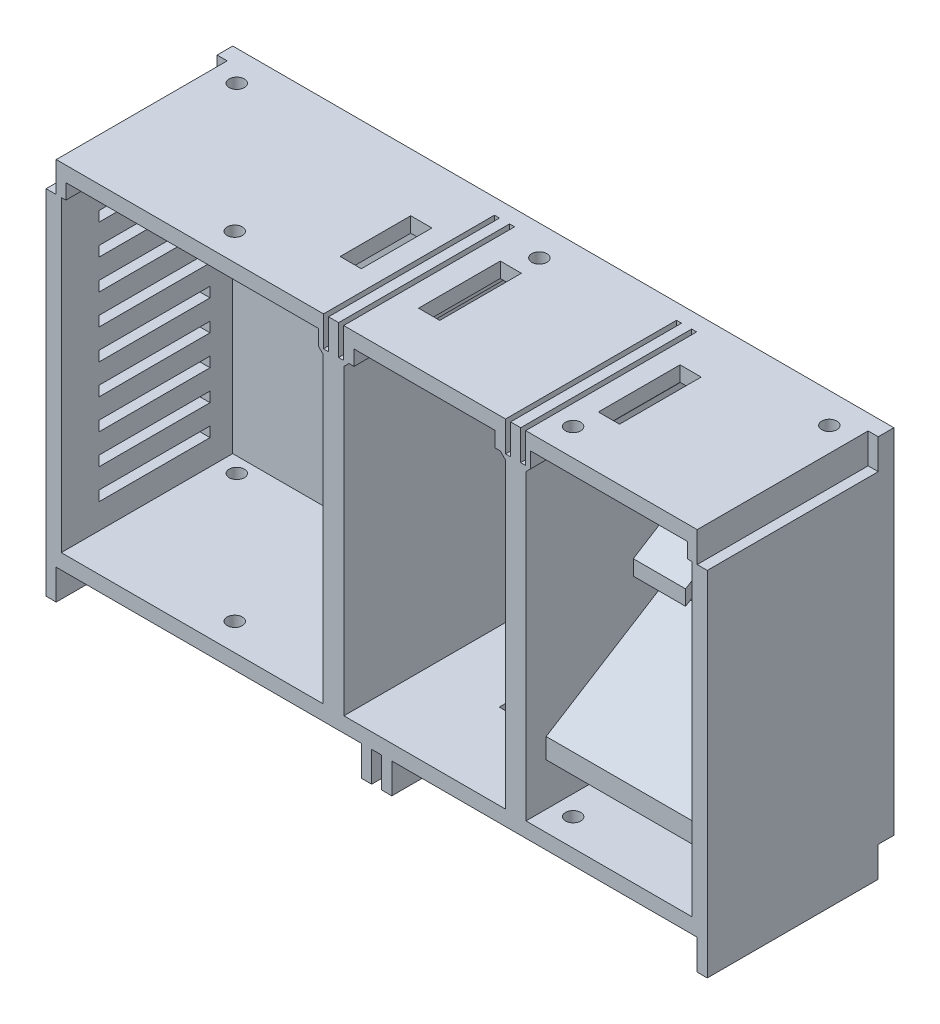
SolidWorks part; units mm, degrees
material "ABS"
ref_plane "Alzado" through (0, 0, 0) normal (0, 0, 1) x (1, 0, 0)
ref_plane "Planta" through (0, 0, 0) normal (0, 1, 0) x (1, 0, 0)
ref_plane "Vista lateral" through (0, 0, 0) normal (1, 0, 0) x (0, 0, -1)
sketch "Croquis1" plane through (0, 0, 0) normal (0, 0, 1) x (1, 0, 0)
  line L0 (0, 0) -> (2, 0)
  line L1 (2, 0) -> (2, 6)
  line L2 (55, 0) -> (55, 6)
  line L3 (55, 6) -> (2, 6)
  line L4 (56, 0) -> (56, 6)
  line L5 (56, 6) -> (58, 6)
  line L6 (58, 6) -> (58, 0)
  line L7 (58, 0) -> (59, 0)
  line L8 (59, 0) -> (59, 6)
  line L9 (91.1, 0) -> (91.1, 6)
  line L10 (59, 6) -> (91.1, 6)
  line L11 (92.1, 0) -> (92.1, 6)
  line L12 (92.1, 6) -> (94.1, 6)
  line L13 (94.1, 6) -> (94.1, 0)
  line L14 (95.1, 0) -> (95.1, 6)
  line L15 (129.1, 0) -> (129.1, 6)
  line L16 (129.1, 6) -> (95.1, 6)
  line L17 (0, 0) -> (0, -64)
  line L18 (0, -64) -> (131.1, -64)
  line L19 (131.1, -64) -> (131.1, 0)
  line L20 (55, 0) -> (56, 0)
  line L21 (58, 0) -> (59, 0)
  line L22 (129.1, 0) -> (131.1, 0)
  line L23 (94.1, 0) -> (95.1, 0)
  line L24 (91.1, 0) -> (92.1, 0)
  line L25 (2, 0) -> (129.1, 0)
  point P3 (2, 0)
  point P4 (129.1, 0)
  point P5 (55, 0)
  point P10 (56, 0)
  point P11 (58, 0)
  point P12 (59, 0)
  point P15 (91.1, 0)
  point P22 (92.1, 0)
  point P23 (94.1, 0)
  point P24 (95.1, 0)
  dimension "D1" = 131.1
  dimension "D2" = 2
  dimension "D3" = 2
  dimension "D4" = 55
  dimension "D5" = 6
  dimension "D6" = 1
  dimension "D7" = 2
  dimension "D8" = 1
  dimension "D9" = 32.1
  dimension "D10" = 1
  dimension "D11" = 2
  dimension "D12" = 1
  dimension "D13" = 64
extrude "Saliente-Extruir1" add sketch "Croquis1" along normal blind 34 contours L8 L25 L9 L10 | L1 L25 L2 L3 | L14 L25 L15 L16 | L11 L25 L13 L12 | L4 L25 L6 L5 region at (28.5, 3, 0) region at (57, 3, 0) region at (112.1, 3, 0) region at (75.05, 3, 0) region at (93.1, 3, 0)
sketch "Croquis2" plane through (0, 0, 0) normal (0, 0, 1) x (1, 0, 0)
  line L1 (2, -64) -> (129.1, -64)
  line L3 (129.1, 0) -> (2, 0)
  line L5 (129.1, 0) -> (131.1, 0)
  line L7 (129.1, -64) -> (131.1, -64)
  line L8 (131.1, 0) -> (131.1, -64)
  line L9 (2, -64) -> (0, -64)
  line L11 (2, 0) -> (0, 0)
  line L12 (0, -64) -> (0, 0)
  dimension "D1" = 64
  dimension "D2" = 2
  dimension "D3" = 2
extrude "Saliente-Extruir2" add sketch "Croquis2" along normal blind 3
sketch "Croquis3" plane through (0, 0, 3) normal (0, 0, 1) x (1, 0, 0)
  line L0 (0, -64) -> (131.1, -64) construction
  line L1 (131.1, 0) -> (128.1, 0)
  line L2 (131.1, 0) -> (131.1, -64)
  line L3 (131.1, -64) -> (128.1, -64)
  line L4 (128.1, 0) -> (128.1, -61)
  line L6 (0, 0) -> (3, 0)
  line L7 (0, 0) -> (0, -64)
  line L8 (0, -64) -> (3, -64)
  line L9 (3, 0) -> (3, -61)
  line L10 (3, -64) -> (128.1, -64)
  line L12 (3, -61) -> (128.1, -61)
  dimension "D1" = 3
  dimension "D2" = 3
  dimension "D3" = 3
extrude "Saliente-Extruir3" add sketch "Croquis3" along normal up to vertex (31 mm away) up to point (129.1, 0, 34)
sketch "Croquis4" plane through (0, 0, 0) normal (0, 0, -1) x (-1, 0, 0)
  line L24 (-59, 0) -> (-59, 6)
  line L25 (-59, 6) -> (-91.1, 6)
  line L26 (-91.1, 6) -> (-91.1, 0)
  line L27 (-91.1, 0) -> (-92.1, 0)
  line L28 (-92.1, 0) -> (-92.1, 6)
  line L29 (-92.1, 6) -> (-94.1, 6)
  line L30 (-94.1, 6) -> (-94.1, 0)
  line L31 (-94.1, 0) -> (-95.1, 0)
  line L32 (-95.1, 0) -> (-95.1, 6)
  line L33 (-95.1, 6) -> (-129.1, 6)
  line L34 (-129.1, 6) -> (-129.1, 0)
  line L35 (-129.1, 0) -> (-131.1, 0)
  line L36 (-131.1, 0) -> (-131.1, -64)
  line L37 (-131.1, -64) -> (0, -64)
  line L38 (0, -64) -> (0, 0)
  line L39 (0, 0) -> (-2, 0)
  line L40 (-2, 0) -> (-2, 6)
  line L41 (-2, 6) -> (-55, 6)
  line L42 (-55, 6) -> (-55, 0)
  line L43 (-55, 0) -> (-56, 0)
  line L44 (-56, 0) -> (-56, 6)
  line L45 (-56, 6) -> (-58, 6)
  line L46 (-58, 6) -> (-58, 0)
  line L47 (-58, 0) -> (-59, 0)
  line L48 (-59, 0) -> (-59, 6)
  line L49 (-59, 6) -> (-91.1, 6)
  line L50 (-91.1, 6) -> (-91.1, 0)
  line L51 (-91.1, 0) -> (-92.1, 0)
  line L52 (-92.1, 0) -> (-92.1, 6)
  line L53 (-92.1, 6) -> (-94.1, 6)
  line L54 (-94.1, 6) -> (-94.1, 0)
  line L55 (-94.1, 0) -> (-95.1, 0)
  line L56 (-95.1, 0) -> (-95.1, 6)
  line L57 (-95.1, 6) -> (-129.1, 6)
  line L58 (-129.1, 6) -> (-129.1, 0)
  line L59 (-129.1, 0) -> (-131.1, 0)
  line L60 (-131.1, 0) -> (-131.1, -64)
  line L61 (-131.1, -64) -> (0, -64)
  line L62 (0, -64) -> (0, 0)
  line L63 (0, 0) -> (-2, 0)
  line L64 (-2, 0) -> (-2, 6)
  line L65 (-2, 6) -> (-55, 6)
  line L66 (-55, 6) -> (-55, 0)
  line L67 (-55, 0) -> (-56, 0)
  line L68 (-56, 0) -> (-56, 6)
  line L69 (-56, 6) -> (-58, 6)
  line L70 (-58, 6) -> (-58, 0)
  line L71 (-58, 0) -> (-59, 0)
  dimension "D1" = 0
extrude "Saliente-Extruir4" add sketch "Croquis4" along normal blind 3
sketch "Croquis5" plane through (0, 0, 3) normal (0, 0, 1) x (1, 0, 0)
  line L1 (128.1, -61) -> (3, -61) construction
  line L23 (54.95, 0.05) -> (59.05, 0.05)
  line L24 (55, 0) -> (55, 6) construction
  line L25 (59, 0) -> (59, 6) construction
  line L26 (58, 0) -> (56, 0) construction
  line L27 (54.95, 0.05) -> (54.95, -61)
  line L28 (59.05, 0.05) -> (59.05, -61)
  line L29 (91.05, 0.05) -> (95.15, 0.05)
  line L30 (91.1, 0) -> (91.1, 6) construction
  line L31 (95.1, 0) -> (95.1, 6) construction
  line L32 (95.1, 0) -> (94.1, 0) construction
  line L33 (91.05, 0.05) -> (91.05, -61)
  line L34 (128.1, -61) -> (3, -61) construction
  line L35 (91.05, -61) -> (95.15, -61)
  line L36 (95.15, -61) -> (95.15, 0.05)
  line M6 (128.1, 0) -> (95.1, 0)
  line M7 (95.1, 0) -> (94.1, 0)
  line M8 (94.1, 0) -> (92.1, 0)
  line M9 (92.1, 0) -> (91.1, 0)
  line M10 (91.1, 0) -> (59, 0)
  line M11 (59, 0) -> (58, 0)
  line M12 (58, 0) -> (56, 0)
  line M13 (56, 0) -> (55, 0)
  line M14 (55, 0) -> (3, 0)
  line M16 (3, -61) -> (128.1, -61)
  dimension "D1" = 0.05
  dimension "D2" = 0.05
  dimension "D3" = 0.05
  dimension "D4" = 0.05
  dimension "D5" = 0.05
  dimension "D6" = 0.05
extrude "Saliente-Extruir10" add sketch "Croquis5" along normal up to vertex (31 mm away) contours L28 L27 M10 M11 M12 M13 M14 M16 | L36 L33 M16 M6 M7 M8 M9 M10 region at (57, -30.5, 3) region at (93.1, -30.5, 3) up to point (59, 0, 34)
sketch "Croquis6" plane through (0, 0, 0) normal (0, -1, 0) x (1, 0, 0)
  line L0 (0, 34) -> (0, -3) construction
  line L1 (0, 15.5) -> (131.1, 15.5) construction
  line L2 (131.1, 34) -> (131.1, -3) construction
  line L3 (51, 8.5) -> (51, 22.5)
  line L4 (51, 22.5) -> (46.8, 22.5)
  line L5 (46.8, 22.5) -> (46.8, 8.5)
  line L6 (46.8, 8.5) -> (51, 8.5)
  line L7 (99.1, 7.4) -> (99.1, 23.6)
  line L8 (99.1, 23.6) -> (103.3, 23.6)
  line L9 (103.3, 23.6) -> (103.3, 7.4)
  line L10 (103.3, 7.4) -> (99.1, 7.4)
  line L11 (63.45, 7.4) -> (63.45, 23.6)
  line L12 (63.45, 23.6) -> (67.65, 23.6)
  line L13 (67.65, 23.6) -> (67.65, 7.4)
  line L14 (67.65, 7.4) -> (63.45, 7.4)
  point P6 (99.1, 15.5)
  point P9 (51, 15.5)
  point P15 (99.1, 15.5)
  point P17 (63.45, 15.5)
  point P21 (63.45, 15.5)
  dimension "D1" = 51
  dimension "D2" = 4.2
  dimension "D3" = 14
  dimension "D4" = 32
  dimension "D5" = 16.2
  dimension "D6" = 4.2
  dimension "D7" = 12.45
extrude "Cortar-Extruir1" cut sketch "Croquis6" against normal up to next
sketch "Croquis7" plane through (0, 0, 34) normal (0, 0, 1) x (1, 0, 0)
  line L0 (3, 0) -> (54.95, 0) construction
  line L1 (28.975, 0) -> (28.975, 3)
  line L2 (3.925, 3) -> (54.025, 3)
  line L3 (54.025, 3) -> (54.025, 0)
  line L4 (3.925, 0) -> (54.025, 0)
  line L5 (3.925, 3) -> (3.925, 0)
  line L6 (75.05, 0) -> (75.05, 3)
  line L7 (59.05, 0) -> (91.05, 0) construction
  line L8 (75.05, 3) -> (89.05, 3)
  line L9 (89.05, 3) -> (89.05, 0)
  line L10 (89.05, 0) -> (75.05, 0)
  line L11 (75.05, 3) -> (61.05, 3)
  line L12 (61.05, 3) -> (61.05, 0)
  line L13 (61.05, 0) -> (75.05, 0)
  line L14 (61.05, 3) -> (75.05, 3)
  line L15 (111.625, 0) -> (111.625, 3)
  line L16 (95.15, 0) -> (128.1, 0) construction
  line L17 (111.625, 3) -> (127.225, 3)
  line L18 (127.225, 3) -> (127.225, 0)
  line L19 (127.225, 0) -> (111.625, 0)
  line L20 (111.625, 0) -> (96.025, 0)
  line L21 (96.025, 0) -> (96.025, 3)
  line L22 (96.025, 3) -> (111.625, 3)
  line M5 (59.05, 0) -> (91.05, 0)
  line M10 (95.15, 0) -> (128.1, 0)
  line M37 (3, 0) -> (54.95, 0)
  dimension "D1" = 25.05
  dimension "D2" = 3
  dimension "D3" = 14
  dimension "D4" = 15.6
extrude "Cortar-Extruir2" cut sketch "Croquis7" against normal up to vertex (31 mm away) contours L3 L2 L1 M37 | L2 L5 L1 M37 | L11 L12 L6 M5 | L9 L8 L6 M5 | L22 L21 L15 M10 | L18 L17 L15 M10 region at (16.45, 1.5, 34) region at (41.5, 1.5, 34) region at (68.05, 1.5, 34) region at (82.05, 1.5, 34) region at (103.825, 1.5, 34) region at (119.425, 1.5, 34) up to point (54.95, 0, 3)
sketch "Croquis22" plane through (0, 0, 3) normal (0, 0, 1) x (1, 0, 0)
  line L0 (95.15, 0) -> (95.15, -61) construction
  line L1 (95.15, -61) -> (128.1, -61) construction
  line L2 (128.1, -61) -> (128.1, 0) construction
  line L3 (128.1, 0) -> (127.225, 0) construction
  line L4 (127.225, 0) -> (127.225, 3) construction
  line L5 (127.225, 3) -> (96.025, 3) construction
  line L6 (96.025, 3) -> (96.025, 0) construction
  line L7 (96.025, 0) -> (95.15, 0) construction
  line L8 (91.05, -61) -> (91.05, 0) construction
  line L9 (91.05, 0) -> (89.05, 0) construction
  line L10 (89.05, 0) -> (89.05, 3) construction
  line L11 (89.05, 3) -> (61.05, 3) construction
  line L12 (61.05, 3) -> (61.05, 0) construction
  line L13 (61.05, 0) -> (59.05, 0) construction
  line L14 (59.05, 0) -> (59.05, -61) construction
  line L15 (59.05, -61) -> (91.05, -61) construction
  line L16 (54.95, -61) -> (54.95, 0) construction
  line L17 (54.95, 0) -> (54.025, 0) construction
  line L18 (54.025, 0) -> (54.025, 3) construction
  line L19 (54.025, 3) -> (3.925, 3) construction
  line L20 (3.925, 3) -> (3.925, 0) construction
  line L21 (3.925, 0) -> (3, 0) construction
  line L22 (3, 0) -> (3, -61) construction
  line L23 (3, -61) -> (54.95, -61) construction
  line L24 (95.15, 0) -> (95.15, -61)
  line L25 (95.15, -61) -> (128.1, -61)
  line L26 (128.1, -61) -> (128.1, 0)
  line L27 (128.1, 0) -> (127.225, 0)
  line L28 (127.225, 0) -> (127.225, 3)
  line L29 (127.225, 3) -> (96.025, 3)
  line L30 (96.025, 3) -> (96.025, 0)
  line L31 (96.025, 0) -> (95.15, 0)
  line L32 (91.05, -61) -> (91.05, 0)
  line L33 (91.05, 0) -> (89.05, 0)
  line L34 (89.05, 0) -> (89.05, 3)
  line L35 (89.05, 3) -> (61.05, 3)
  line L36 (61.05, 3) -> (61.05, 0)
  line L37 (61.05, 0) -> (59.05, 0)
  line L38 (59.05, 0) -> (59.05, -61)
  line L39 (59.05, -61) -> (91.05, -61)
  line L40 (54.95, -61) -> (54.95, 0)
  line L41 (54.95, 0) -> (54.025, 0)
  line L42 (54.025, 0) -> (54.025, 3)
  line L43 (54.025, 3) -> (3.925, 3)
  line L44 (3.925, 3) -> (3.925, 0)
  line L45 (3.925, 0) -> (3, 0)
  line L46 (3, 0) -> (3, -61)
  line L47 (3, -61) -> (54.95, -61)
extrude "Cortar-Extruir8" cut sketch "Croquis22" against normal blind 3 contours L40 L41 L42 L43 L44 L45 L46 L47 | L32 L33 L34 L35 L36 L37 L38 L39 | L24 L25 L26 L27 L28 L29 L30 L31
sketch "Croquis24" plane through (2, 0, 0) normal (-1, 0, 0) x (0, 0, 1)
  line L0 (34, 0) -> (-3, 0) construction
  line L5 (0.1, 0) -> (-4.3164, 0)
  line L6 (0.1, 0) -> (0.1, 6.5451)
  line L7 (0.1, 6.5451) -> (-4.3164, 6.5451)
  line L8 (-4.3164, 0) -> (-4.3164, 6.5451)
  line L9 (0, 0) -> (0, 8.0802) construction
  dimension "D1" = 0.1
extrude "Cortar-Extruir11" cut sketch "Croquis24" against normal through all contours L6 L5 L8 L7
sketch "Croquis25" plane through (0, 0, 0.1) normal (0, 0, -1) x (-1, 0, 0)
  line L1 (-2, 0) -> (-55, 0)
  line L2 (-2, 0) -> (-2, 6)
  line L3 (-2, 6) -> (-55, 6)
  line L4 (-55, 0) -> (-55, 6)
  line L5 (-59, 6) -> (-91.1, 6)
  line L6 (-59, 6) -> (-59, 0)
  line L7 (-59, 0) -> (-91.1, 0)
  line L8 (-91.1, 6) -> (-91.1, 0)
  line L9 (-95.1, 6) -> (-129.1, 6)
  line L10 (-95.1, 6) -> (-95.1, 0)
  line L11 (-95.1, 0) -> (-129.1, 0)
  line L12 (-129.1, 6) -> (-129.1, 0)
extrude "Saliente-Extruir15" add sketch "Croquis25" against normal blind 1
sketch "Croquis26" plane through (0, 0, 0) normal (0, 0, 1) x (1, 0, 0)
  line L0 (4, -60) -> (54.1, -60)
  line L1 (4, -60) -> (4, -4.1)
  line L2 (4, -4.1) -> (54.1, -4.1)
  line L3 (54.1, -60) -> (54.1, -4.1)
  line L4 (4, -60) -> (54.1, -4.1) construction
  line L5 (4, -4.1) -> (54.1, -60) construction
  line L6 (36.1, -45) -> (46.1, -45)
  line L7 (36.1, -45) -> (36.1, -39)
  line L8 (36.1, -39) -> (46.1, -39)
  line L9 (46.1, -45) -> (46.1, -39)
  line L10 (3, -61) -> (54.95, -61) construction
  line L11 (3, 0) -> (3, -61) construction
  line L12 (54.95, -61) -> (54.95, 0) construction
  circle A0 centre (24, -8.1) radius 1
  circle A1 centre (8, -18.9) radius 1
  circle A2 centre (24, -8.1) radius 2.5
  circle A3 centre (8, -18.9) radius 2.5
  point P0 (29.05, -32.05)
  point P5 (24, -8.1)
  point P8 (8, -18.9)
  dimension "D6" = 2
  dimension "D7" = 5
  dimension "D1" = 1
  dimension "D2" = 55.9
  dimension "D3" = 1
  dimension "D4" = 4
  dimension "D5" = 14.8
  dimension "D8" = 4
  dimension "D9" = 20
  dimension "D10" = 8
  dimension "D11" = 15
  dimension "D12" = 6
  dimension "D13" = 10
  dimension "D14" = 0.85
extrude "Saliente-Extruir16" add sketch "Croquis26" along normal blind 6 contours L6 L9 L8 L7 | A2 A0 | A3 A1 region at (41.1, -42, 0) region at (21.5707, -8.1, 0) region at (5.5707, -18.9, 0)
fillet "Redondeo1" radius 2.4 3 edges at (10.5, -18.9, 0) (26.5, -8.1, 0) (46.1, -42, 0)
chamfer "Chaflán1" distance 1 angle 45 4 edges at (54.95, 0, 17.05) (95.15, 0, 17.05) (91.05, 0, 17.05) (59.05, 0, 17.05)
sketch "Croquis10" plane through (0, 0, 0) normal (-1, 0, 0) x (0, 0, 1)
  line L0 (15.5, -64) -> (15.5, 6) construction
  line L1 (34, -64) -> (-3, -64) construction
  line L3 (4.5, -50) -> (4.5, -48)
  line L4 (4.5, -56) -> (26.5, -56)
  line L5 (4.5, -56) -> (4.5, -54)
  line L6 (4.5, -54) -> (26.5, -54)
  line L7 (26.5, -56) -> (26.5, -54)
  line L8 (4.5, -56) -> (26.5, -54) construction
  line L9 (4.5, -54) -> (26.5, -56) construction
  line L10 (4.5, -50) -> (26.5, -50)
  line L11 (26.5, -50) -> (26.5, -48)
  line L12 (4.5, -48) -> (26.5, -48)
  line L13 (4.5, -44) -> (4.5, -42)
  line L14 (4.5, -44) -> (26.5, -44)
  line L15 (26.5, -44) -> (26.5, -42)
  line L16 (4.5, -42) -> (26.5, -42)
  line L17 (4.5, -38) -> (4.5, -36)
  line L18 (4.5, -38) -> (26.5, -38)
  line L19 (26.5, -38) -> (26.5, -36)
  line L20 (4.5, -36) -> (26.5, -36)
  line L21 (4.5, -32) -> (4.5, -30)
  line L22 (4.5, -32) -> (26.5, -32)
  line L23 (26.5, -32) -> (26.5, -30)
  line L24 (4.5, -30) -> (26.5, -30)
  line L25 (4.5, -26) -> (4.5, -24)
  line L26 (4.5, -26) -> (26.5, -26)
  line L27 (26.5, -26) -> (26.5, -24)
  line L28 (4.5, -24) -> (26.5, -24)
  line L29 (4.5, -20) -> (4.5, -18)
  line L30 (4.5, -20) -> (26.5, -20)
  line L31 (26.5, -20) -> (26.5, -18)
  line L32 (4.5, -18) -> (26.5, -18)
  line L33 (4.5, -14) -> (4.5, -12)
  line L34 (4.5, -14) -> (26.5, -14)
  line L35 (26.5, -14) -> (26.5, -12)
  line L36 (4.5, -12) -> (26.5, -12)
  line L37 (4.5, -8) -> (4.5, -6)
  line L38 (4.5, -8) -> (26.5, -8)
  line L39 (26.5, -8) -> (26.5, -6)
  line L40 (4.5, -6) -> (26.5, -6)
  point P6 (15.5, -55)
  dimension "D1" = 22
  dimension "D2" = 2
  dimension "D3" = 8
  dimension "D4" = 9
extrude "Cortar-Extruir3" cut sketch "Croquis10" against normal up to vertex (3 mm away) contours L4 L7 L6 L5 | L12 L3 L10 L11 | L16 L13 L14 L15 | L20 L17 L18 L19 | L24 L21 L22 L23 | L28 L25 L26 L27 | L32 L29 L30 L31 | L36 L33 L34 L35 | L40 L37 L38 L39 region at (0, -49, 15.5) region at (0, -55, 15.5) region at (0, -43, 15.5) region at (0, -37, 15.5) region at (0, -31, 15.5) region at (0, -25, 15.5) region at (0, -19, 15.5) region at (0, -13, 15.5) region at (0, -7, 15.5) up to point (3, -61, 34)
sketch "Croquis12" plane through (95.15, 0, 0) normal (1, 0, 0) x (0, 0, -1)
  line L0 (0, -29.7544) -> (-34, -51)
  line L1 (0, 0) -> (0, -61) construction
  line L2 (-34, -61) -> (-34, -1) construction
  line L4 (-34, -51) -> (-34, -55)
  line L5 (-34, -55) -> (0, -33.7544)
  line L6 (0, -29.7544) -> (0, -33.7544)
  dimension "D1" = 4
  dimension "D2" = 58
  dimension "D3" = 6
extrude "Saliente-Extruir12" add sketch "Croquis12" along normal up to surface (32.95 mm away) up to face at (128.1, -24.4, 13.62)
sketch "Croquis13" plane through (95.15, 0, 0) normal (1, 0, 0) x (0, 0, -1)
  line L0 (0, -29.7544) -> (0, -21.6544) construction
  line L2 (0, -21.6544) -> (-12.7207, -29.6032)
  line L4 (0, -29.7544) -> (-34, -51) construction
  line L6 (-12.7207, -26.6032) -> (0, -18.6544)
  line L7 (0, -18.6544) -> (0, -21.6544)
  line L8 (-12.7207, -29.6032) -> (-12.7207, -26.6032)
  line L9 (-34, -51) -> (-8.7351, -35.2127) construction
  line L10 (0, -29.7544) -> (-34, -51) construction
  line L11 (-6.7844, -33.9938) -> (-6.7844, -25.8938)
  line L12 (-6.7844, -33.9938) -> (0, -29.7544)
  line L13 (0, 0) -> (0, -29.7544) construction
  line M8 (-34, -51) -> (0, -29.7544)
  line M18 (0, -29.7544) -> (0, 0)
  dimension "D1" = 8.1
  dimension "D2" = 3
  dimension "D3" = 15
  dimension "D4" = 8
extrude "Saliente-Extruir17" add sketch "Croquis13" along normal up to surface (32.95 mm away) contours L11 L2 M8 M18 | L8 L2 L6 M18 region at (95.15, -27.8241, 3.3922) region at (95.15, -24.1288, 6.3604) up to face at (128.1, -16.1509, 13.62)
ref_plane "Plano1" through (0, -18.6544, 0) normal (0, -1, 0) x (-1, 0, 0)
sketch "Croquis38" plane through (0, -18.6544, 0) normal (0, -1, 0) x (-1, 0, 0)
  line L0 (-111.625, 0) -> (-111.625, -34.0311) construction
  line L1 (-128.1, 0) -> (-95.15, 0) construction
  line L2 (-111.625, 0) -> (-117.725, 0)
  line L3 (-117.725, 0) -> (-117.725, -26)
  line L4 (-117.725, -26) -> (-105.525, -26)
  line L5 (-111.625, 0) -> (-105.525, 0)
  line L6 (-105.525, 0) -> (-105.525, -26)
  dimension "D1" = 6.1
  dimension "D2" = 6.1
  dimension "D3" = 26
  dimension "D4" = 26
extrude "Cortar-Extruir12" cut sketch "Croquis38" along normal up to vertex (15.3394 mm away) contours L0 L2 L3 L4 | L5 L0 L4 L6 region at (108.575, -18.6544, 13) region at (114.675, -18.6544, 13) up to point (128.1, -33.9938, 6.7844)
sketch "Croquis40" plane through (0, 3, 0) normal (0, -1, 0) x (1, 0, 0)
  line L0 (0, 34) -> (0, -3) construction
  line L1 (3.925, 34) -> (54.025, 34) construction
  line L2 (131.1, 34) -> (131.1, -3) construction
  line L3 (0, -3) -> (131.1, -3) construction
  circle A0 centre (32, 28.6) radius 1.5
  circle A1 centre (99.1, 28.6) radius 1.5
  circle A2 centre (6.8, 3) radius 1.5
  circle A3 centre (124.3, 3) radius 1.5
  circle A4 centre (66.8, 3) radius 1.5
  dimension "D3" = 3
  dimension "D1" = 32
  dimension "D2" = 5.4
  dimension "D4" = 32
  dimension "D5" = 6.8
  dimension "D6" = 6
  dimension "D7" = 6.8
  dimension "D8" = 60
extrude "Cortar-Extruir13" cut sketch "Croquis40" against normal up to next
sketch "Croquis42" plane through (0, 0, 0) normal (0, -1, 0) x (1, 0, 0)
  line L0 (90.05, 0.1) -> (90.05, 34) construction
  line L1 (96.15, 0.1) -> (127.225, 0.1)
  line L2 (96.15, 0.1) -> (96.15, 1.1)
  line L3 (96.15, 1.1) -> (127.225, 1.1)
  line L4 (127.225, 0.1) -> (127.225, 1.1)
  line L5 (60.05, 0.1) -> (90.05, 0.1)
  line L6 (60.05, 0.1) -> (60.05, 1.1)
  line L7 (60.05, 1.1) -> (90.05, 1.1)
  line L8 (90.05, 0.1) -> (90.05, 1.1)
  line L9 (3, 34) -> (3, 0.1) construction
  line L10 (3, 1.1) -> (53.8965, 1.1)
  line L11 (3, 1.1) -> (3, 0)
  line L12 (3, 0) -> (53.8965, 0)
  line L13 (53.8965, 1.1) -> (53.8965, 0)
  line L14 (54.95, 0) -> (3, 0) construction
extrude "Saliente-Extruir18" add sketch "Croquis42" along normal blind 0.2
sketch "Croquis44" plane through (0, 0, 0) normal (0, 0, 1) x (1, 0, 0)
  line L0 (90.05, -0.2) -> (60.05, -0.2) construction
  line L1 (62.35, -22.2) -> (87.75, -22.2)
  line L2 (62.35, -22.2) -> (62.35, -56)
  line L3 (62.35, -56) -> (87.75, -56)
  line L4 (87.75, -22.2) -> (87.75, -56)
  line L5 (59.05, -1) -> (59.05, -61) construction
  line L6 (59.05, -61) -> (91.05, -61) construction
  line L7 (75.05, -56) -> (75.05, -22.2) construction
  line L8 (62.35, -39.1) -> (87.75, -39.1) construction
  circle A0 centre (65.65, -53.7) radius 2.5
  circle A1 centre (65.65, -53.7) radius 1.2
  circle A2 centre (84.25, -53.7) radius 2.5
  circle A3 centre (84.25, -53.7) radius 1.2
  circle A4 centre (84.75, -24.2) radius 2.5
  circle A5 centre (84.75, -24.2) radius 1.2
  circle A6 centre (65.35, -24.2) radius 2.5
  circle A7 centre (65.35, -24.2) radius 1.2
  point P6 (75.05, -0.2)
  point P7 (75.05, -22.2)
  point P8 (75.05, -56)
  dimension "D4" = 5
  dimension "D5" = 2.4
  dimension "D1" = 25.4
  dimension "D2" = 33.8
  dimension "D3" = 5
  dimension "D6" = 3.3
  dimension "D7" = 2.3
  dimension "D8" = 2.3
  dimension "D9" = 3.5
  dimension "D10" = 3
  dimension "D11" = 2
  dimension "D12" = 3
  dimension "D13" = 2
extrude "Saliente-Extruir19" add sketch "Croquis44" along normal blind 3 contours L3 A2 | L3 A2 A3 | L3 A0 | L3 A0 A1 | L1 A6 A7 | L1 A6 | L1 A4 A5 | L1 A4 region at (65.35, -21.9982, 0) region at (65.35, -22.2673, 0) region at (64.3097, -51.6722, 0) region at (65.65, -56.0803, 0) region at (84.75, -21.9982, 0) region at (84.75, -22.2673, 0) region at (82.9097, -51.6722, 0) region at (84.25, -56.0803, 0)
fillet "Redondeo2" radius 3 4 edges at (86.75, -53.7, 0) (68.15, -53.7, 0) (87.25, -24.2, 0) (67.85, -24.2, 0)
sketch "Croquis48" plane through (0, 0, 0) normal (-1, 0, 0) x (0, 0, 1)
  line L1 (-3, 0) -> (0.1, 0)
  line L2 (-3, 0) -> (-3, 6)
  line L3 (-3, 6) -> (0.1, 6)
  line L4 (0.1, 0) -> (0.1, 6)
extrude "Saliente-Extruir20" add sketch "Croquis48" against normal up to vertex (131.1 mm away) up to point (131.1, 0, -3)
sketch "Croquis49" plane through (0, 0, 34) normal (0, 0, 1) x (1, 0, 0)
  line L0 (2, 0) -> (2, -64) construction
  line L1 (0, -64) -> (131.1, -64) construction
  line L2 (129.1, 0) -> (129.1, -64) construction
  line L3 (66.55, -70) -> (66.55, -64)
  line L4 (2, -64) -> (0, -64)
  line L5 (0, -64) -> (0, -70)
  line L6 (0, -70) -> (2, -70)
  line L7 (2, -70) -> (2, -64)
  line L8 (129.1, -64) -> (131.1, -64)
  line L9 (131.1, -64) -> (131.1, -70)
  line L10 (131.1, -70) -> (129.1, -70)
  line L11 (129.1, -70) -> (129.1, -64)
  line L12 (65.55, -64) -> (68.55, -64)
  line L13 (68.55, -64) -> (68.55, -70)
  line L14 (68.55, -70) -> (66.55, -70)
  line L15 (62.55, -70) -> (62.55, -64)
  line L16 (62.55, -64) -> (65.55, -64)
  line L17 (64.55, -70) -> (64.55, -64)
  line L18 (64.55, -70) -> (62.55, -70)
  dimension "D1" = 6
  dimension "D2" = 3
  dimension "D3" = 2
  dimension "D4" = 2
extrude "Saliente-Extruir21" add sketch "Croquis49" against normal up to vertex (33.9 mm away) contours L6 L7 L4 L5 | L18 L17 L16 L15 | L14 L13 L12 L3 | L11 L10 L9 L8 region at (63.55, -67, 34) region at (67.55, -67, 34) region at (1, -67, 34) region at (130.1, -67, 34) up to point (2, 0, 0.1)
sketch "Croquis50" plane through (0, -64, 0) normal (0, -1, 0) x (1, 0, 0)
  circle A0 centre (124.3, 3) radius 1.5 construction
  circle A1 centre (99.1, 28.6) radius 1.5 construction
  circle A3 centre (6.8, 3) radius 1.5 construction
  circle A4 centre (32, 28.6) radius 1.5 construction
  circle A5 centre (124.3, 3) radius 1.5
  circle A6 centre (99.1, 28.6) radius 1.5
  circle A8 centre (6.8, 3) radius 1.5
  circle A9 centre (32, 28.6) radius 1.5
extrude "Cortar-Extruir14" cut sketch "Croquis50" against normal up to surface (3 mm away) up to face at (28.975, -61, 17)
sketch "Croquis51" plane through (0, 0, 0) normal (-1, 0, 0) x (0, 0, 1)
  line L0 (0.1, -64) -> (-3, -64) construction
  line L1 (-3, 6) -> (-2.9, 6)
  line L2 (-3, 6) -> (-3, -64)
  line L3 (-3, -64) -> (-2.9, -64)
  line L4 (-2.9, 6) -> (-2.9, -64)
  dimension "D1" = 0.1
extrude "Cortar-Extruir15" cut sketch "Croquis51" against normal through all
sketch "Croquis52" plane through (0, -64, 0) normal (0, -1, 0) x (1, 0, 0)
  line L0 (68.55, 0.1) -> (68.55, 34) construction
  line L1 (72.95, 17.1) -> (78.95, 17.1)
  line L2 (72.95, 17.1) -> (72.95, 9.1)
  line L3 (72.95, 9.1) -> (78.95, 9.1)
  line L4 (78.95, 17.1) -> (78.95, 9.1)
  line L5 (131.1, -2.9) -> (0, -2.9) construction
  dimension "D1" = 4.4
  dimension "D2" = 12
  dimension "D3" = 8
  dimension "D4" = 6
extrude "Cortar-Extruir16" cut sketch "Croquis52" against normal up to vertex (3 mm away) up to point (59.05, -61, 34)
sketch "Croquis53" plane through (0, 0, 34) normal (0, 0, 1) x (1, 0, 0)
  line L0 (128.1, 0) -> (128.1, -51) construction
  line L1 (95.15, -51) -> (128.1, -51)
  line L2 (95.15, -51) -> (95.15, -55)
  line L3 (95.15, -55) -> (128.1, -55)
  line L4 (128.1, -51) -> (128.1, -55)
  line L5 (95.15, -51) -> (128.1, -51)
  line L6 (95.15, -51) -> (95.15, -48.3278)
  line L7 (95.15, -48.3278) -> (128.1, -48.3278)
  line L8 (128.1, -51) -> (128.1, -48.3278)
extrude "Cortar-Extruir17" cut sketch "Croquis53" against normal blind 4 contours L4 L1 L2 L3 | L1 L8 L7 L6 region at (111.625, -49.6639, 34) region at (111.625, -53, 34)
sketch "Croquis54" plane through (0, 0, -2.9) normal (0, 0, -1) x (-1, 0, 0)
  line L1 (-131.1, 6) -> (0, 6)
  line L2 (-131.1, 6) -> (-131.1, -64)
  line L3 (-131.1, -64) -> (0, -64)
  line L4 (0, 6) -> (0, -64)
extrude "Saliente-Extruir22" add sketch "Croquis54" along normal blind 0.1
